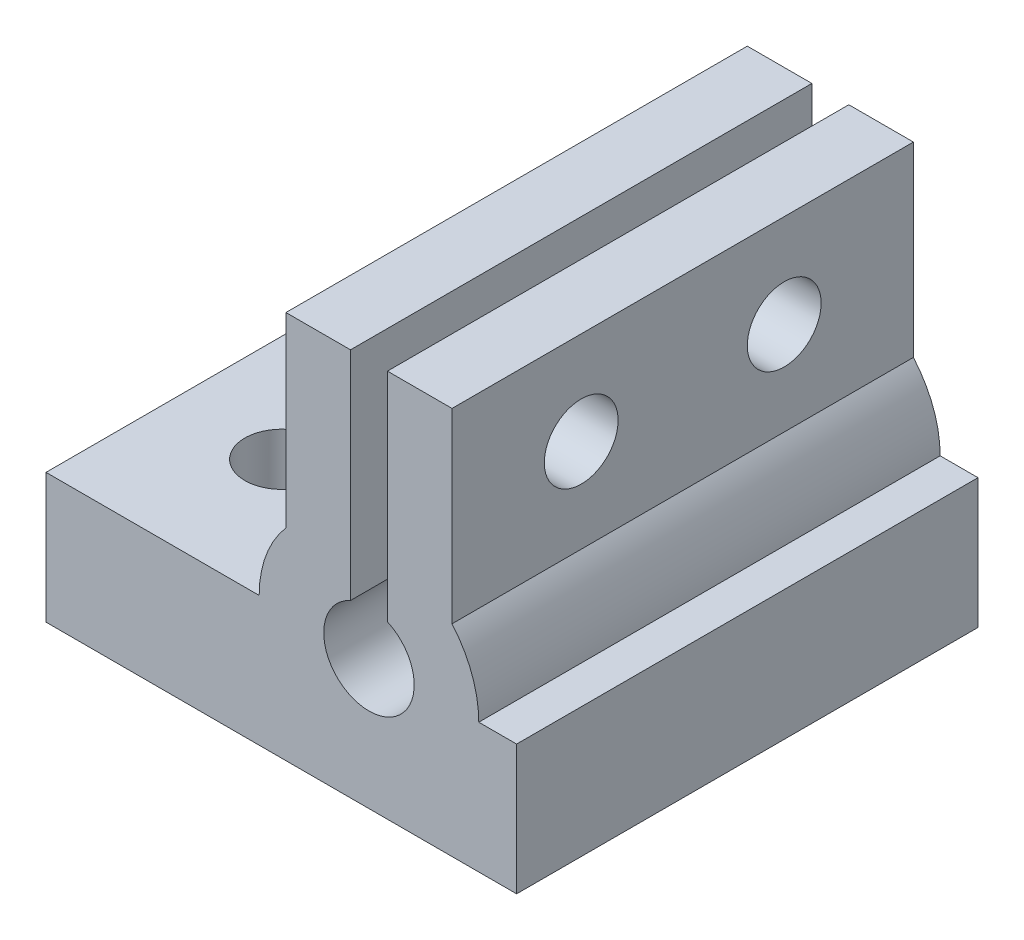
SolidWorks part; units mm, degrees
ref_plane "Front Plane" through (0, 0, 0) normal (0, 0, 1) x (1, 0, 0)
ref_plane "Top Plane" through (0, 0, 0) normal (0, 1, 0) x (1, 0, 0)
ref_plane "Right Plane" through (0, 0, 0) normal (1, 0, 0) x (0, 0, -1)
sketch "Sketch1" plane through (0, 0, 0) normal (0, 0, 1) x (1, 0, 0)
  line L0 (0, 0) -> (35, 0)
  line L1 (35, 0) -> (35, 7.03)
  line L2 (35, 7.03) -> (23.45, 7.03)
  line L3 (11.55, 7.03) -> (0, 7.03)
  line L4 (0, 7.03) -> (0, 0)
  line L5 (13, 10.9226) -> (13, 21.03)
  line L6 (13, 21.03) -> (16.5, 21.03)
  line L7 (16.5, 21.03) -> (16.5, 9.2666)
  line L8 (17.5, 0) -> (17.5, 21.03) construction
  line L9 (18.5, 9.2666) -> (18.5, 21.03)
  line L10 (18.5, 21.03) -> (22, 21.03)
  line L11 (22, 21.03) -> (22, 10.9226)
  arc A0 (23.45, 7.03) -> (22, 10.9226) centre (17.5, 7.03) ccw
  arc A1 (13, 10.9226) -> (11.55, 7.03) centre (17.5, 7.03) ccw
  arc A2 (16.5, 9.2666) -> (18.5, 9.2666) centre (17.5, 7.03) ccw
  dimension "D1" = 4.9
  dimension "D4" = 14
  dimension "D6" = 3.5
  dimension "D2" = 35
  dimension "D3" = 7.03
  dimension "D5" = 3.5
  dimension "D7" = 2
extrude "Boss-Extrude1" add sketch "Sketch1" along normal blind 25
sketch "Sketch2" plane through (22, 0, 0) normal (1, 0, 0) x (0, 0, -1)
  line L0 (-25, 15.9763) -> (0, 15.9763) construction
  line L1 (-25, 10.9226) -> (-25, 21.03) construction
  line L2 (0, 10.9226) -> (0, 21.03) construction
  circle A0 centre (-18, 15.9763) radius 2
  circle A1 centre (-7, 15.9763) radius 2
  dimension "D3" = 4
  dimension "D1" = 7
  dimension "D2" = 7
extrude "Cut-Extrude1" cut sketch "Sketch2" against normal up to surface (9 mm away) up to face at (13, 15.9763, 12.5)
sketch "Sketch3" plane through (0, 7.03, 0) normal (0, 1, 0) x (1, 0, 0)
  line L0 (29.225, -25) -> (29.225, 0) construction
  line L1 (35, -25) -> (23.45, -25) construction
  line L2 (35, 0) -> (23.45, 0) construction
  line L3 (17.5, -25) -> (17.5, 0) construction
  line L4 (0, 0) -> (35, 0) construction
  line L5 (0, -25) -> (35, -25) construction
  circle A0 centre (29.225, -18) radius 2
  circle A1 centre (29.225, -7) radius 2
  circle A2 centre (5.775, -7) radius 2
  circle A3 centre (5.775, -18) radius 2
  dimension "D2" = 7
  dimension "D3" = 4
  dimension "D1" = 7
extrude "Cut-Extrude2" cut sketch "Sketch3" against normal up to next
sketch "Sketch4" plane through (0, 7.03, 0) normal (0, 1, 0) x (1, 0, 0)
  line L0 (35, 0) -> (23.45, 0) construction
  line L1 (35, -25) -> (25.5, -25)
  line L2 (35, -25) -> (35, 0)
  line L3 (35, 0) -> (25.5, 0)
  line L4 (25.5, -25) -> (25.5, 0)
  dimension "D1" = 9.5
extrude "Cut-Extrude3" cut sketch "Sketch4" against normal up to next
